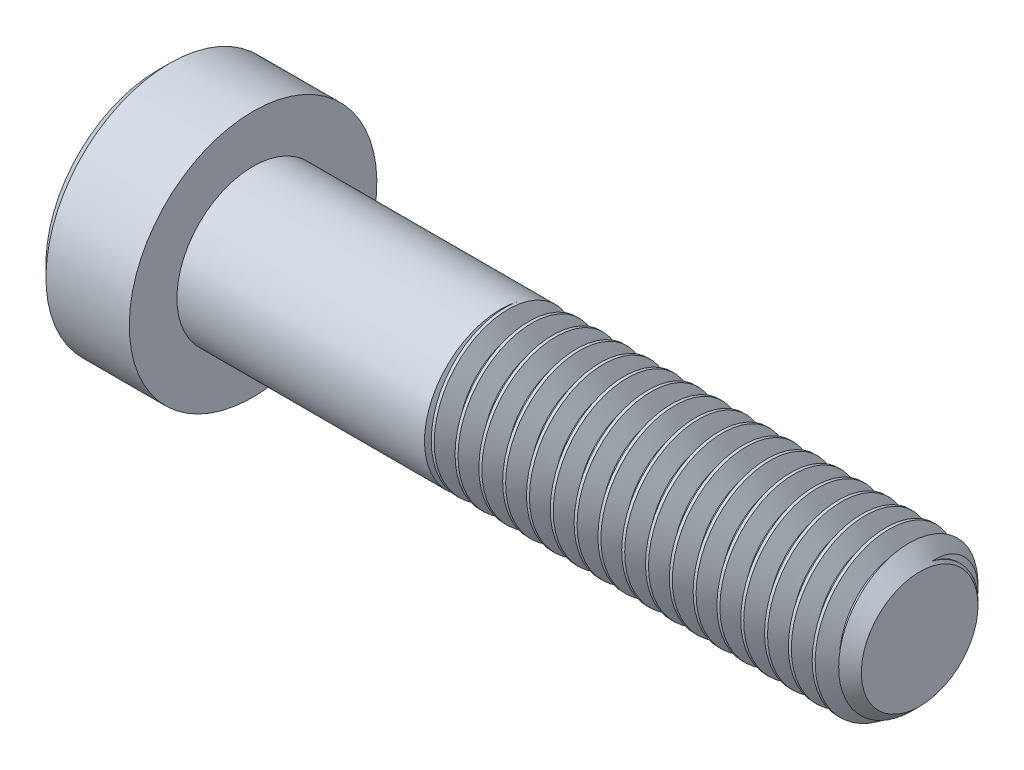
SolidWorks part; units mm, degrees
ref_plane "Front Plane" through (0, 0, 0) normal (0, 0, 1) x (1, 0, 0)
ref_plane "Top Plane" through (0, 0, 0) normal (0, 1, 0) x (1, 0, 0)
ref_plane "Right Plane" through (0, 0, 0) normal (1, 0, 0) x (0, 0, -1)
sketch "Sketch1" plane through (0, 0, 0) normal (0, 0, 1) x (1, 0, 0)
  line L0 (17.5, 0) -> (-17.5, 0) construction
  line L1 (17.5, 4) -> (17.5, -4) construction
  line L2 (-17.5, 6.5) -> (-17.5, -6.5) construction
  line L3 (-17.5, 6.5) -> (-21.875, 6.5) construction
  line L4 (-21.875, 6.5) -> (-22.5, 5.875) construction
  line L5 (-22.5, 5.875) -> (-22.5, -5.875) construction
  line L6 (-22.5, -5.875) -> (-21.875, -6.5) construction
  line L7 (-21.875, -6.5) -> (-17.5, -6.5) construction
  line L8 (-4.5, 4) -> (-4.5, -4) construction
  point P7 (-18.55, 0)
  point P12 (12.5, -4)
  dimension "D1" = 45
  dimension "Dec." = 8
  dimension "Length" = 35
  dimension "Head Dia" = 13
  dimension "Head Height" = 5
  dimension "Hex Depth" = 3.95
  dimension "Chamfer" = 0.625
  dimension "D2" = 5
  dimension "Thread Length" = 22
ref_plane "Plane1" through (17.5, 0, 0) normal (1, 0, 0) x (0, 0, -1)
ref_plane "Plane2" through (-22.5, 0, 0) normal (1, 0, 0) x (0, 0, -1)
sketch "Sketch2" plane through (17.5, 0, 0) normal (1, 0, 0) x (0, 0, -1)
  circle A0 centre (0, 0) radius 4
extrude "Boss-Extrude1" add sketch "Sketch2" against normal up to vertex (22 mm away) up to point (-4.5, 4, 0)
sketch "Sketch3" plane through (17.5, 0, 0) normal (1, 0, 0) x (0, 0, -1)
  circle A0 centre (0, 0) radius 4 construction
  circle A1 centre (0, 0) radius 4
curve "Helix/Spiral1" pitch 1.25 height 23.25 radius 4 centre (17.5, 0, 0) axis (-1, 0, 0) start towards (0, 1, 0) parameters "Pitch"=1.25
chamfer "Chamfer1" distance 0.9375 angle 45 1 edges at (17.5, 0, -4)
sketch "Sketch5" plane through (0, 0, 0) normal (0, 0, 1) x (1, 0, 0)
  line L0 (16.9531, 4) -> (18.0469, 4)
  line L1 (18.0469, 4) -> (17.5781, 3.1881)
  line L2 (17.5781, 3.1881) -> (17.4219, 3.1881)
  line L3 (17.4219, 3.1881) -> (16.9531, 4)
  line L4 (17.5, 3.1881) -> (17.5, 4) construction
  line L5 (17.1875, 3.5941) -> (17.8125, 3.5941) construction
  dimension "D1" = 60
  dimension "D2" = 0.625
  dimension "D3" = 0.1562
sweep "Cut-Sweep1" cut profiles "Sketch5" path "Helix/Spiral1" align with end faces yes
sketch "Sketch4" plane through (-22.5, 0, 0) normal (1, 0, 0) x (0, 0, -1)
  line L0 (-6.5, 0.7937) -> (6.5, 0.7937) construction
  line L1 (0, 2.8868) -> (-2.5, 1.4434)
  line L2 (-2.5, 1.4434) -> (-2.5, -1.4434)
  line L3 (-2.5, -1.4434) -> (0, -2.8868)
  line L4 (0, -2.8868) -> (2.5, -1.4434)
  line L5 (2.5, -1.4434) -> (2.5, 1.4434)
  line L6 (2.5, 1.4434) -> (0, 2.8868)
  line L7 (0, 0) -> (0, 0.7937) construction
  circle A0 centre (0, 0) radius 2.5 construction
  dimension "Hex Size" = 5
  dimension "D1" = 13
  dimension "D2" = 0.7937
sketch "Sketch10" plane through (0, 0, 0) normal (0, 0, 1) x (1, 0, 0)
  line L0 (-17.5, 0) -> (-2.1906, 0) construction
  line L1 (-2.1906, 0) -> (-4.5, 4)
  line L2 (-4.5, 4) -> (-17.5, 4)
  line L3 (-17.5, 4) -> (-17.5, 0)
  line L4 (-17.5, 6.5) -> (-17.5, -6.5) construction
  line L5 (-17.5, 0) -> (-2.1906, 0)
  dimension "D1" = 60
revolve "Revolve2" add sketch "Sketch10" angle 360 about L0
sketch "Sketch6" plane through (0, 0, 0) normal (0, 0, 1) x (1, 0, 0)
  line L0 (-21.875, 6.5) -> (-22.5, 5.875) construction
  line L1 (-17.5, 6.5) -> (-21.875, 6.5) construction
  line L2 (-17.5, 6.5) -> (-17.5, -6.5) construction
  line L3 (-22.5, 5.875) -> (-22.5, -5.875) construction
  line L4 (-21.875, 6.5) -> (-22.5, 5.875)
  line L5 (-17.5, 6.5) -> (-21.875, 6.5)
  line L6 (-17.5, 6.5) -> (-17.5, 0)
  line L7 (-22.5, 5.875) -> (-22.5, 0)
  line L8 (-17.5, 0) -> (-22.5, 0) construction
  line L9 (-17.5, 0) -> (-22.5, 0)
revolve "Revolve1" add sketch "Sketch6" angle 360 about L8
extrude "Cut-Extrude1" cut sketch "Sketch4" along normal up to vertex (3.95 mm away) up to point (-18.55, 0, 0)
sketch "Sketch8" plane through (-22.5, 0, 0) normal (-1, 0, 0) x (0, 0, 1)
  circle A1 centre (0, 0) radius 2.8868
extrude "Cut-Extrude2" cut sketch "Sketch8" against normal through all draft 45
equation "\"D3@Helix/Spiral1\" = \"Thread Length@Sketch1\"+\"Pitch@Helix/Spiral1\""
equation "\"D3@Sketch5\" = \"Pitch@Helix/Spiral1\"*.125"
equation "\"D2@Sketch5\" = \"Pitch@Helix/Spiral1\"*.50"
equation "\"D1@Chamfer1\" = \"Pitch@Helix/Spiral1\"*.75"
equation "\"D2@Sketch1\" = \"Pitch@Helix/Spiral1\"*4"
equation "\"D1@Sketch4\" = \"Head Dia@Sketch1\""
equation "\"Chamfer@Sketch1\" = \"Head Height@Sketch1\"/8"
